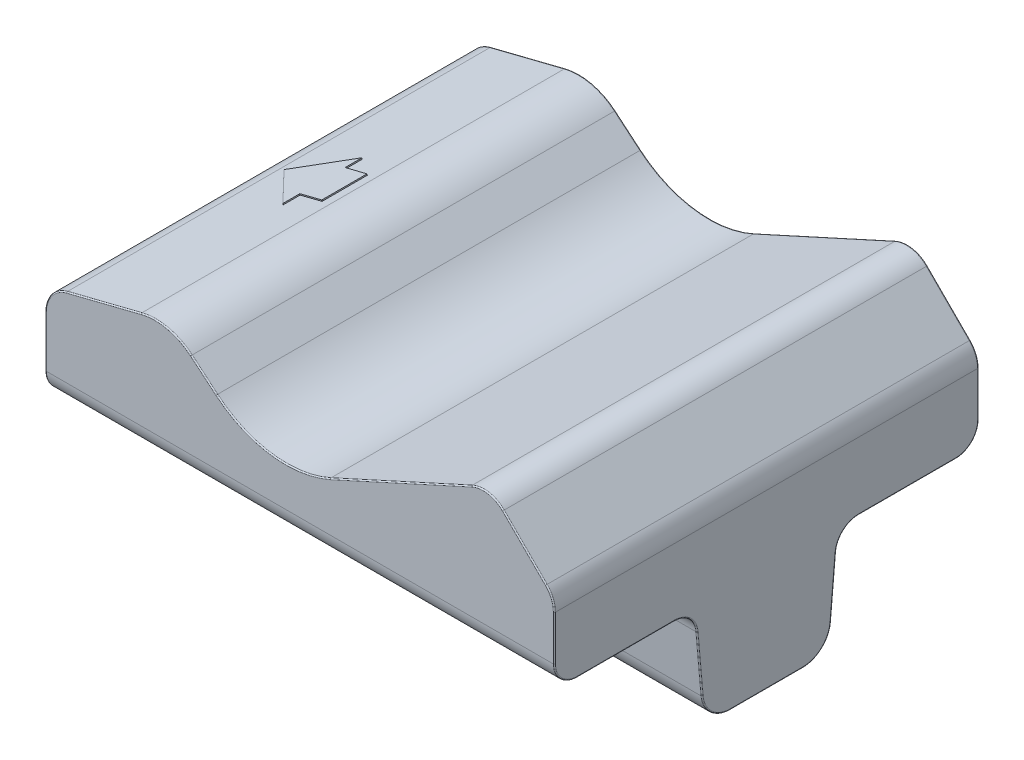
SolidWorks part; units mm, degrees
material "ИРП-1078А"
ref_plane "Спереди" through (0, 0, 0) normal (0, 0, 1) x (1, 0, 0)
ref_plane "Сверху" through (0, 0, 0) normal (0, 1, 0) x (1, 0, 0)
ref_plane "Справа" through (0, 0, 0) normal (1, 0, 0) x (0, 0, -1)
sketch "Эскиз1" plane through (0, 0, 0) normal (0, 0, 1) x (1, 0, 0)
  line L0 (0, -19) -> (6.3444, -19) construction
  line L1 (7.8659, -17.2953) -> (36, -4.5)
  line L2 (47.5, -16) -> (47.5, -31)
  line L3 (47.5, -31) -> (-42.5, -31)
  line L4 (-42.5, -31) -> (-42.5, -13)
  line L5 (47.5, -16) -> (36, -4.5)
  line L6 (-20.6206, -7.5) -> (-12.213, -14.5548)
  line L7 (-42.5, -13) -> (-20.6206, -7.5)
  arc A0 (7.8659, -17.2953) -> (-12.213, -14.5548) centre (0, 0) cw
  point P8 (0, 0)
  dimension "D5" = 19
  dimension "D6" = 31
  dimension "D2" = 42.5
  dimension "D1" = 90
  dimension "D3" = 40
  dimension "D4" = 26.5
  dimension "D7" = 18
  dimension "D8" = 23.5
  dimension "D9" = 24.456
  dimension "D10" = 15
  dimension "D11" = 45
  dimension "D12" = 12
extrude "Бобышка-Вытянуть1" add sketch "Эскиз1" along normal blind 37.5 and the other way blind 37.5
other "Переместить грань3" flip direction yes face at (2.5, -31, 0) offset 1 parameters "D1"=1
sketch "Эскиз4" plane through (-42.5, 0, 0) normal (-1, 0, 0) x (0, 0, 1)
  line L0 (0, -30) -> (0, -39.3975) construction
  line L1 (-37.5, -30) -> (37.5, -30) construction
  line L2 (-12.6185, -30) -> (-11, -48.5)
  line L3 (-11, -48.5) -> (11, -48.5)
  line L4 (12.6185, -30) -> (11, -48.5)
  line L5 (-12.6185, -30) -> (12.6185, -30)
  point P9 (0, -48.5)
  dimension "D1" = 10
  dimension "D2" = 22
  dimension "D3" = 18.5
extrude "Бобышка-Вытянуть3" add sketch "Эскиз4" against normal up to surface (90 mm away) up to face at (47.5, -23, 0)
fillet "Скругление1" radius 5 3 edges at (47.5, -16, 0) (36, -4.5, 0) (-42.5, -13, 0)
fillet "Скругление2" radius 4 2 edges
fillet "Скругление3" radius 5 2 edges at (2.5, -48.5, 11) (2.5, -48.5, -11)
sketch "Эскиз5" plane through (0.5477, -2.1788, 0) normal (-0.2438, 0.9698, 0) x (0.9698, 0.2438, 0)
  line L0 (0, 0) -> (-40.4883, 0) construction
  line L1 (-40.4883, 37.5) -> (-40.4883, -37.5) construction
  line L2 (-39.4883, 0) -> (-32.4883, 7)
  line L3 (-32.4883, 7) -> (-32.4883, 4)
  line L4 (-32.4883, 4) -> (-28.4883, 4)
  line L5 (-28.4883, 4) -> (-28.4883, -4)
  line L6 (-39.4883, 0) -> (-32.4883, -7)
  line L7 (-32.4883, -7) -> (-32.4883, -4)
  line L8 (-32.4883, -4) -> (-28.4883, -4)
  point P13 (-28.4883, 0)
  dimension "D1" = 45
  dimension "D2" = 7
  dimension "D3" = 4
  dimension "D4" = 1
  dimension "D5" = 8
fillet "Скругление16" radius 10 1 edges at (-20.6206, -7.5, 0)
sketch "Эскиз9" plane through (0, 0, 0) normal (1, 0, 0) x (0, 0, -1)
  line L0 (15.9664, -30.0126) -> (13.5, -44)
  line L2 (13.5, -44) -> (11.3933, -44)
  line L3 (12.2991, -33.6514) -> (11.3993, -43.9358) construction
  line L4 (0, 0) -> (0, -36.831) construction
  line L5 (12.2991, -33.6514) -> (11.3993, -43.9358)
  line L6 (-13.5, -44) -> (-11.3933, -44)
  line L9 (-12.2991, -33.6514) -> (-11.3993, -43.9358)
  line L10 (-15.9664, -30.0126) -> (-13.5, -44)
  line L11 (37.5, -30) -> (16.2839, -30) construction
  arc A0 (16.2839, -30) -> (12.2991, -33.6514) centre (16.2839, -34) ccw construction
  arc A2 (6.4183, -48.5) -> (11.3993, -43.9358) centre (6.4183, -43.5) ccw construction
  arc A5 (15.9664, -30.0126) -> (12.2991, -33.6514) centre (16.2839, -34) ccw
  arc A6 (-15.9664, -30.0126) -> (-12.2991, -33.6514) centre (-16.2839, -34) cw
  arc A7 (11.3933, -44) -> (11.3993, -43.9358) centre (6.4183, -43.5) ccw
  arc A8 (-11.3933, -44) -> (-11.3993, -43.9358) centre (-6.4183, -43.5) cw
  dimension "D2" = 27
  dimension "D1" = 14
  dimension "D3" = 10
extrude "Бобышка-Вытянуть5" add sketch "Эскиз9" along normal blind 6 and the other way blind 6
fillet "Скругление14" radius 2 4 edges at (-6, -44, -12.4466) (6, -44, -12.4466) (-6, -44, 12.4466) (6, -44, 12.4466)
fillet "Скругление15" radius 0.2 30 edges at (6, -36.0063, -14.9095) (5.4142, -43.4142, -13.6033) (0, -44, -13.5) (-5.4142, -43.4142, -13.6033) (-6, -36.0063, -14.9095) (-6, -31.1606, -13.4665) (-6, -37.8257, -11.9339) (-5.582, -43.2236, -11.4616) (0, -44, -11.3933) (5.582, -43.2236, -11.4616) (6, -31.1606, -13.4665) (6, -37.8257, -11.9339) (0, -30.0126, -15.9664) (0, -30.0126, 15.9664) (-6, -31.1606, 13.4665) (-6, -37.8257, 11.9339) (6, -31.1606, 13.4665) (6, -37.8257, 11.9339) (6, -36.0063, 14.9095) (-6, -36.0063, 14.9095) (5.582, -43.2236, 11.4616) (0, -44, 11.3933) (-5.582, -43.2236, 11.4616) (-5.4142, -43.4142, 13.6033) (0, -44, 13.5) (5.4142, -43.4142, 13.6033)
fillet "Скругление17" radius 4 2 edges at (2.5, -30, -37.5) (2.5, -30, 37.5)
fillet "Скругление19" radius 0.2 44 edges at (47.5, -28.8284, -36.3284) (47.5, -31.0509, -13.5815) (47.5, -47.1864, -9.7963) (47.5, -48.5, 0) (47.5, -47.1864, 9.7963) (47.5, -31.0509, 13.5815) (47.5, -28.8284, 36.3284) (47.5, -22.0355, 37.5) (47.1194, -16.1577, 37.5) (42.2431, -10.7431, 37.5) (35.8067, -5.5663, 37.5) (20.3555, -11.6151, 37.5) (-2.5694, -18.8255, 37.5) (-14.4605, -12.6689, 37.5) (-20.8959, -8.6976, 37.5) (-32.1464, -10.3973, 37.5) (-41.443, -13.8242, 37.5) (-42.5, -21.4493, 37.5) (-42.5, -28.8284, 36.3284) (-42.5, -31.0509, 13.5815) (-42.5, -47.1864, 9.7963) (-42.5, -48.5, 0) (-42.5, -47.1864, -9.7963) (-42.5, -31.0509, -13.5815) (-42.5, -28.8284, -36.3284) (47.1194, -16.1577, -37.5) (42.2431, -10.7431, -37.5) (35.8067, -5.5663, -37.5) (20.3555, -11.6151, -37.5) (-2.5694, -18.8255, -37.5) (-14.4605, -12.6689, -37.5) (-20.8959, -8.6976, -37.5) (-32.1464, -10.3973, -37.5) (-41.443, -13.8242, -37.5) (-42.5, -21.4493, -37.5) (47.5, -22.0355, -37.5)
extrude "Бобышка-Вытянуть6" add sketch "Эскиз5" along normal blind 0.2
